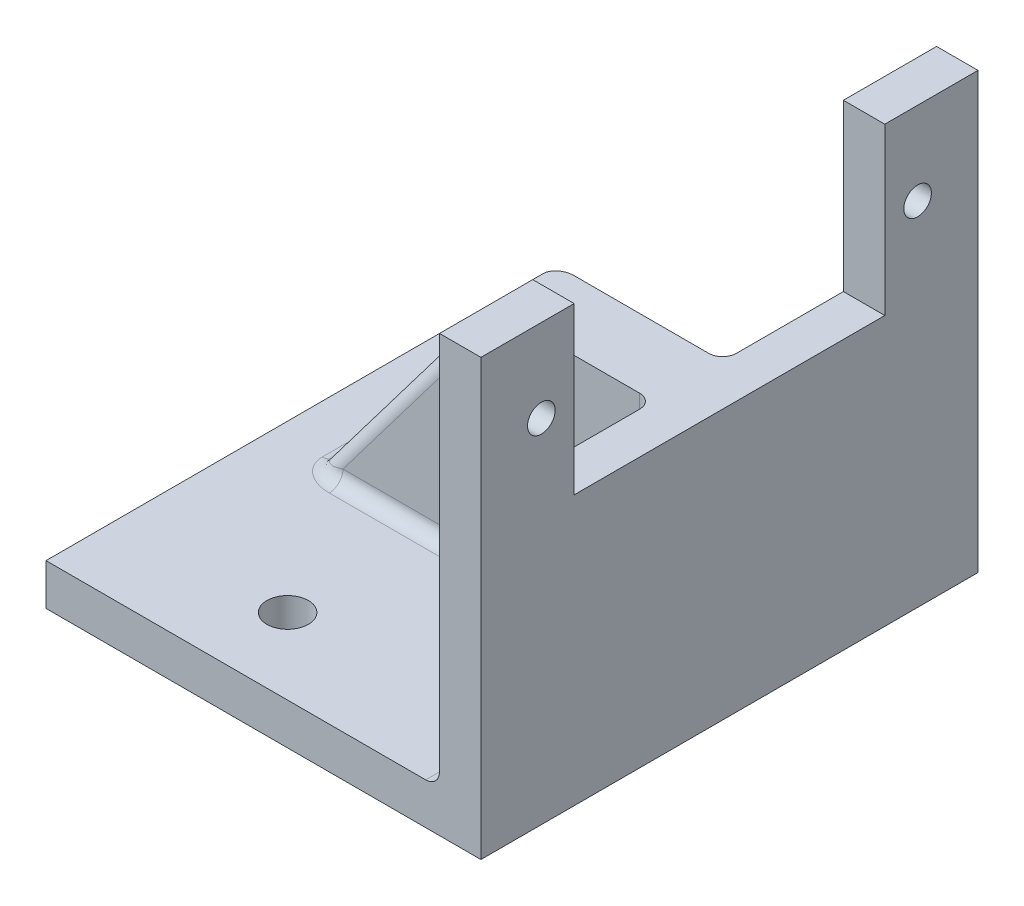
SolidWorks part; units mm, degrees
ref_plane "Front Plane" through (0, 0, 0) normal (0, 0, 1) x (1, 0, 0)
ref_plane "Top Plane" through (0, 0, 0) normal (0, 1, 0) x (1, 0, 0)
ref_plane "Right Plane" through (0, 0, 0) normal (1, 0, 0) x (0, 0, -1)
sketch "Sketch1" plane through (0, 0, 0) normal (0, 0, 1) x (1, 0, 0)
  line L0 (0, 0) -> (0, 30)
  line L1 (0, 0) -> (-30, 0)
  dimension "D1" = 30
extrude "Extrude-Thin1" add sketch "Sketch1" along normal mid plane 36 thin thin type mid plane wall 3
sketch "Sketch2" plane through (1.5, 0, 0) normal (1, 0, 0) x (0, 0, -1)
  line L0 (-18, 30) -> (18, 30) construction
  line L1 (-11.25, 30) -> (11.25, 30)
  line L2 (-11.25, 30) -> (-11.25, 18)
  line L3 (-11.25, 18) -> (11.25, 18)
  line L4 (11.25, 30) -> (11.25, 18)
  line L5 (-18, -1.5) -> (18, -1.5) construction
  point P6 (0, 18)
  point P9 (0, -1.5)
  dimension "D1" = 22.5
  dimension "D2" = 12
extrude "Cut-Extrude1" cut sketch "Sketch2" against normal through all
sketch "Sketch3" plane through (1.5, 0, 0) normal (1, 0, 0) x (0, 0, -1)
  line L0 (0, 18) -> (0, 24) construction
  line L3 (-11.25, 18) -> (11.25, 18) construction
  circle A0 centre (-13.625, 24) radius 1
  circle A1 centre (13.625, 24) radius 1
  dimension "D1" = 27.25
  dimension "D2" = 13.625
extrude "Cut-Extrude2" cut sketch "Sketch3" against normal through all
sketch "Sketch5" plane through (0, 0, 0) normal (0, 0, 1) x (1, 0, 0)
  line L0 (-1.5, 1.5) -> (-30, 1.5) construction
  line L1 (-1.5, 1.5) -> (-26, 1.5)
  line L2 (-1.5, 1.5) -> (-1.5, 18)
  line L3 (-1.5, 18) -> (-13.5, 18)
  line L4 (-13.5, 18) -> (-26, 1.5)
  dimension "D1" = 4
  dimension "D2" = 12
extrude "Boss-Extrude1" add sketch "Sketch5" along normal mid plane 5
fillet "Fillet1" radius 1 2 edges at (-19.75, 9.75, -2.5) (-19.75, 9.75, 2.5)
fillet "Fillet2" radius 1 9 edges at (-13.1227, 1.5, -2.5) (-25.6325, 1.5, -2.2071) (-26, 1.5, 0) (-25.6325, 1.5, 2.2071) (-1.5, 1.5, -10.25) (-1.5, 1.5, 10.25) (-1.5, 9.75, -2.5) (-13.1227, 1.5, 2.5) (-1.5, 9.75, 2.5)
sketch "Sketch6" plane through (0, 1.5, 0) normal (0, 1, 0) x (1, 0, 0)
  line L0 (-30, -18) -> (-30, 18) construction
  line L1 (-18, 12.5) -> (-18, -12.5) construction
  circle A0 centre (-18, 12.5) radius 1.5
  circle A1 centre (-18, -12.5) radius 1.5
  point P6 (-18, 0)
  point P7 (-30, 0)
  dimension "D1" = 3
  dimension "D2" = 25
  dimension "D3" = 12
extrude "Cut-Extrude3" cut sketch "Sketch6" against normal through all
